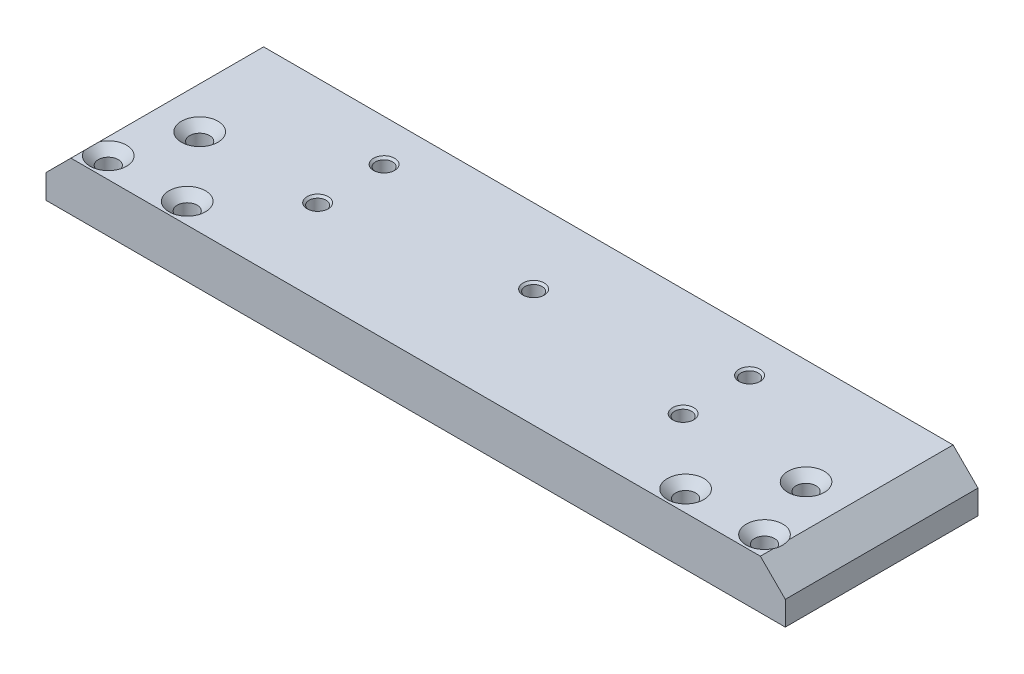
SolidWorks part; units mm, degrees
material "6061-T6 (SS)"
ref_plane "Front Plane" through (0, 0, 0) normal (0, 0, 1) x (1, 0, 0)
ref_plane "Top Plane" through (0, 0, 0) normal (0, 1, 0) x (1, 0, 0)
ref_plane "Right Plane" through (0, 0, 0) normal (1, 0, 0) x (0, 0, -1)
sketch "Sketch1" plane through (0, 0, 0) normal (0, 1, 0) x (1, 0, 0)
  line L1 (44.5, -11.6) -> (-44.5, -11.6)
  line L2 (44.5, -11.6) -> (44.5, 11.6)
  line L3 (44.5, 11.6) -> (-44.5, 11.6)
  line L4 (-44.5, -11.6) -> (-44.5, 11.6)
  line L5 (44.5, -11.6) -> (-44.5, 11.6) construction
  line L6 (44.5, 11.6) -> (-44.5, -11.6) construction
  point P0 (0, 0)
  dimension "D1" = 89
  dimension "D2" = 23.2
extrude "Boss-Extrude1" add sketch "Sketch1" along normal blind 4 and the other way blind 1.9
hole_wizard "M2.5x0.45 Tapped Hole2" positions "Sketch4" profile "Sketch5" tap size "M2.5x0.45" standard "ANSI Metric" end condition through all
sketch "Sketch4" plane through (0, 4, 0) normal (0, 1, 0) x (1, 0, 0)
  line L0 (44.5, 11.6) -> (-44.5, 11.6) construction
  point P0 (-22, 6.6)
  point P2 (-22, -1.4)
  point P4 (22, -1.4)
  point P6 (22, 6.6)
  point P8 (0, 2.6)
  dimension "D1" = 8
  dimension "D2" = 8
  dimension "D3" = 44
  dimension "D4" = 22
  dimension "D5" = 9
  dimension "D6" = 4
  dimension "D7" = 4
cosmetic thread "Hole Thread6" parameters "D2"=2.5
cosmetic thread "Hole Thread7" parameters "D2"=2.5
cosmetic thread "Hole Thread8" parameters "D2"=2.5
cosmetic thread "Hole Thread9" parameters "D2"=2.5
cosmetic thread "Hole Thread10" parameters "D2"=2.5
sketch "Sketch5" plane through (-22, 4, -6.6) normal (1, 0, 0) x (0, 0, 1)
  line L0 (0, 0) -> (0, 5.9)
  line L1 (0, 5.9) -> (1.025, 5.9)
  line L2 (1.025, 5.9) -> (1.025, 0.25)
  line L3 (1.025, 0.25) -> (1.275, 0)
  line L5 (1.275, 0) -> (0, 0)
  line L6 (-1.025, 0.25) -> (-1.275, 0) construction
  line L11 (0, -6.35) -> (0, 107.95) construction
  dimension "Thru Tap Drill Dia." = 2.05
  dimension "Thru Tap Drill Depth" = 5.9
  dimension "Near C'Sink Dia." = 2.55
  dimension "Near C'Sink Angle" = 90
hole_wizard "CSK for M2 Flat Head Machine Screw1" positions "Sketch6" profile "Sketch7" countersink size "M2" standard "ANSI Metric"
sketch "Sketch6" plane through (0, 4, 0) normal (0, 1, 0) x (1, 0, 0)
  line L0 (-44.5, -11.6) -> (44.5, -11.6) construction
  circle A0 centre (0, 2.6) radius 1.025 construction
  point P0 (-36.5, -1.1)
  point P2 (-39.5, -9.1)
  point P4 (-30, -9.1)
  point P6 (30, -9.1)
  point P8 (39.5, -9.1)
  point P10 (36.5, -1.1)
  dimension "D5" = 39.5
  dimension "D1" = 39.5
  dimension "D2" = 3
  dimension "D3" = 8
  dimension "D4" = 9.5
  dimension "D6" = 3
  dimension "D7" = 9.5
  dimension "D8" = 8
  dimension "D9" = 2.5
  dimension "D10" = 2.5
sketch "Sketch7" plane through (-36.5, 4, 1.1) normal (1, 0, 0) x (0, 0, 1)
  line L0 (0, 0) -> (0, 7.171)
  line L1 (0, 7.171) -> (1.2, 6.45)
  line L2 (1.2, 6.45) -> (1.2, 1)
  line L3 (1.2, 1) -> (2.2, 0)
  line L5 (2.2, 0) -> (0, 0)
  line L6 (-1.2, 1) -> (-2.2, 0) construction
  line L10 (0, 7.171) -> (-1.2, 6.45) construction
  line L11 (0, -6.35) -> (0, 107.95) construction
  dimension "Hole Dia." = 2.4
  dimension "Hole Depth" = 6.45
  dimension "Near C'Sink Dia." = 4.4
  dimension "Near C'Sink Angle" = 90
  dimension "Drill Angle" = 118
sketch "Sketch8" plane through (0, 0, 11.6) normal (0, 0, 1) x (1, 0, 0)
  line L9 (41.5, 4) -> (44.5, 4)
  line L10 (-44.5, 4) -> (44.5, 4) construction
  line L11 (44.5, 4) -> (44.5, 1)
  line L12 (44.5, 4) -> (44.5, -1.9) construction
  line L13 (44.5, 1) -> (41.5, 4)
  line L14 (-44.5, 4) -> (-44.5, 1)
  line L15 (-44.5, 4) -> (-44.5, -1.9) construction
  line L16 (-44.5, 1) -> (-41.5, 4)
  line L17 (-41.5, 4) -> (-44.5, 4)
  dimension "D1" = 3
  dimension "D2" = 2.9
  dimension "D3" = 2.9
  dimension "D4" = 3
extrude "Cut-Extrude1" cut sketch "Sketch8" against normal up to surface (23.2 mm away) up to face at (0, 1.05, -11.6)
